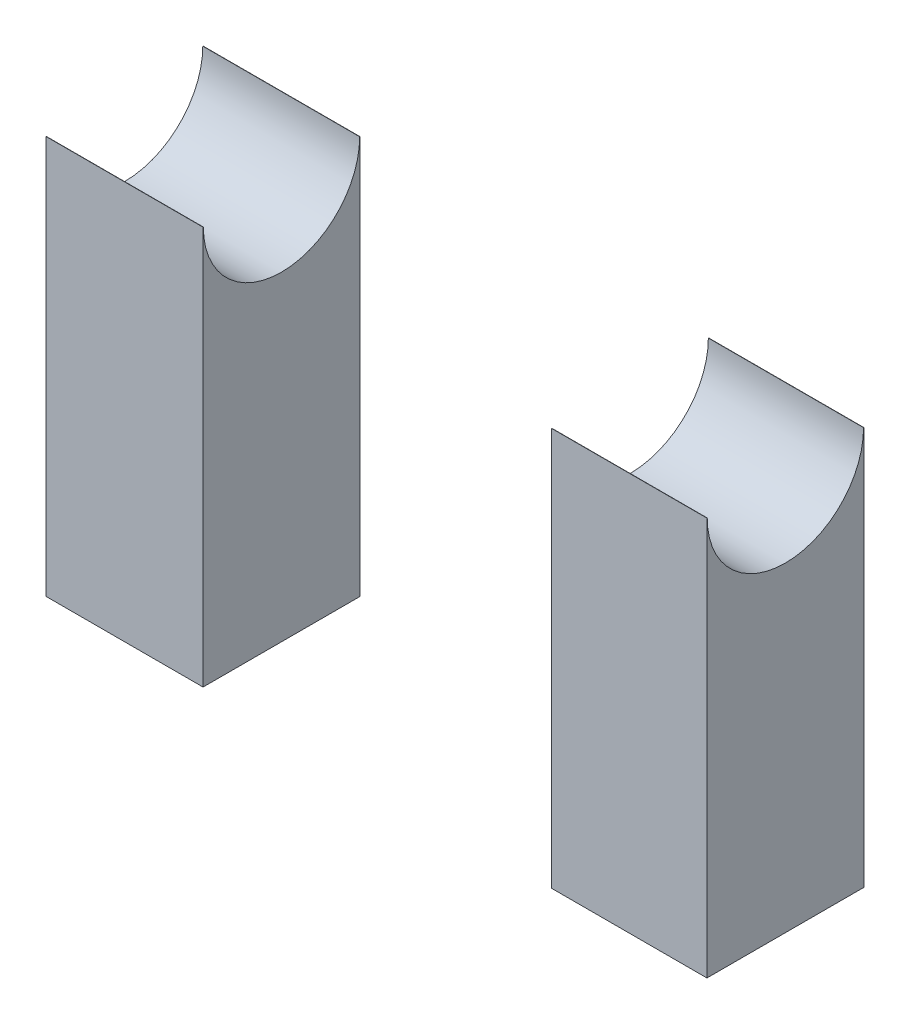
SolidWorks part; units mm, degrees
ref_plane "Ebene vorne" through (0, 0, 0) normal (0, 0, 1) x (1, 0, 0)
ref_plane "Ebene oben" through (0, 0, 0) normal (0, 1, 0) x (1, 0, 0)
ref_plane "Ebene rechts" through (0, 0, 0) normal (1, 0, 0) x (0, 0, -1)
sketch "Skizze1" plane through (0, 0, 0) normal (0, 0, 1) x (1, 0, 0)
  line L0 (0, 0) -> (-4.5, 0)
  line L1 (-4.5, 0) -> (-4.5, 11.4233)
  line L2 (-4.5, 11.4233) -> (0, 11.4233)
  line L3 (0, 11.4233) -> (0, 0)
  line L4 (10, 0) -> (14.4514, 0)
  line L5 (14.4514, 0) -> (14.4514, 11.4233)
  line L6 (14.4514, 11.4233) -> (10, 11.4233)
  line L7 (10, 11.4233) -> (10, 0)
  dimension "D1" = 10
  dimension "D2" = 4.5
  dimension "D3" = 11.4233
  dimension "D4" = 11.4233
  dimension "D5" = 4.4514
extrude "Aufsatz-Linear austragen1" add sketch "Skizze1" along normal blind 4.5
sketch "Skizze2" plane through (-4.5, 0, 0) normal (-1, 0, 0) x (0, 0, 1)
  line L0 (2.25, 11.4233) -> (2.25, 0) construction
  line L1 (4.5, 11.4233) -> (0, 11.4233) construction
  line L2 (4.5, 0) -> (0, 0) construction
  circle A0 centre (2.25, 11.4233) radius 2.2422
  point P2 (2.25, 10.7209)
  point P9 (0, 0)
  point P10 (2.25, 11.3104)
extrude "Schnitt-Linear austragen1" cut sketch "Skizze2" against normal blind 20
